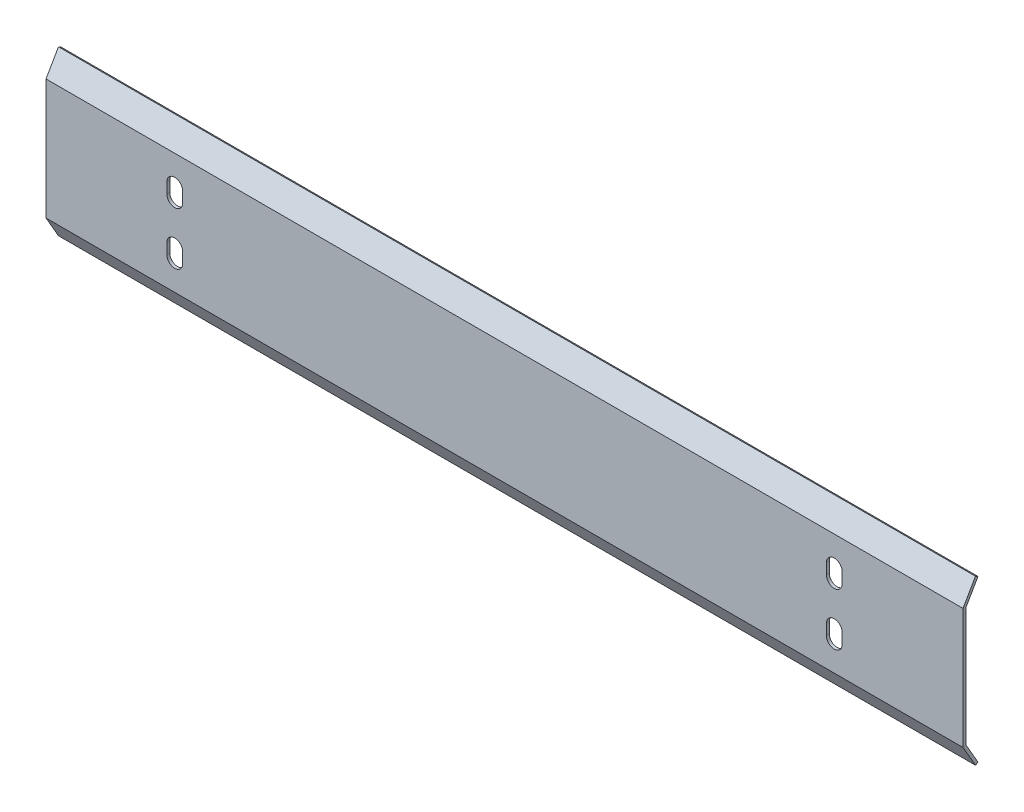
SolidWorks part; units mm, degrees
ref_plane "前视基准面" through (0, 0, 0) normal (0, 0, 1) x (1, 0, 0)
ref_plane "上视基准面" through (0, 0, 0) normal (0, 1, 0) x (1, 0, 0)
ref_plane "右视基准面" through (0, 0, 0) normal (1, 0, 0) x (0, 0, -1)
sketch "草图2" plane through (0, 0, 0) normal (1, 0, 0) x (0, 0, -1)
  line L3 (0, 0) -> (0, 45.8455)
  line L4 (0, 45.8455) -> (4.75, 54.0728)
  line L5 (0, 0) -> (4.75, -8.2272)
  line L6 (1.1, 0.2947) -> (5.7026, -7.6772)
  line L7 (1.1, 0.2947) -> (1.1, 45.5508)
  line L8 (1.1, 45.5508) -> (5.7026, 53.5228)
  line L9 (4.75, -8.2272) -> (5.7026, -7.6772)
  line L10 (5.7026, 53.5228) -> (4.75, 54.0728)
  dimension "D1" = 150
  dimension "D2" = 150
  dimension "D3" = 9.5
  dimension "D4" = 62.3
  dimension "D5" = 1.1
base flange "基体-法兰2" sketch "草图2" thickness 349 reverse thickness direction no parameters "D1"=1
sketch "草图11" plane through (0, 0, 0) normal (0, 0, 1) x (1, 0, 0)
  line L0 (-49, 14.9228) -> (-49, 10.9228) construction
  line L1 (-46, 14.9228) -> (-46, 10.9228)
  line L2 (-52, 14.9228) -> (-52, 10.9228)
  line L3 (0, 45.8455) -> (0, 0) construction
  line L4 (0, 22.9228) -> (-67.8978, 22.9228) construction
  arc A0 (-46, 14.9228) -> (-52, 14.9228) centre (-49, 14.9228) ccw
  arc A1 (-52, 10.9228) -> (-46, 10.9228) centre (-49, 10.9228) ccw
  point P2 (-49, 12.9228)
  dimension "D2" = 3
  dimension "D1" = 49
  dimension "D3" = 4
  dimension "D4" = 10
extrude "切除-拉伸1" cut sketch "草图11" against normal blind 10 normal cut yes
ref_plane "基准面1" through (0, 22.9228, 0) normal (0, 1, 0) x (1, 0, 0)
mirror "镜向1" about plane through (0, 22.9228, 0) normal (0, 1, 0) of "切除-拉伸1"
pattern_linear "阵列(线性)1" count 2 spacing 251 along (-1, 0, 0) of "镜向1", "切除-拉伸1"
sketch "折弯-线3" [suppressed] plane through (0, 0, 0) normal (0, 1, 0) x (1, 0, 0)
sketch "边界框3" [suppressed] plane through (0, 0, 0) normal (0, 1, 0) x (1, 0, 0)
sheet metal parameters "钣金13" thickness 349 parameters "D1"=1
flat pattern "平板型式13" [suppressed]
sketch "折弯-线4" plane through (0, 0, 0) normal (0, 1, 0) x (1, 0, 0)
sketch "边界框4" [suppressed] plane through (0, 0, 0) normal (0, 1, 0) x (1, 0, 0)
sheet metal parameters "钣金14" thickness 349 parameters "D1"=1
flat pattern "平板型式13"
sketch "折弯-线4" plane through (0, 0, 0) normal (0, 1, 0) x (1, 0, 0)
sketch "边界框4" [suppressed] plane through (0, 0, 0) normal (0, 1, 0) x (1, 0, 0)
sheet metal parameters "钣金15" thickness 349 parameters "D1"=1
flat pattern "平板型式13"
sketch "折弯-线4" plane through (0, 0, 0) normal (0, 1, 0) x (1, 0, 0)
sketch "边界框4" [suppressed] plane through (0, 0, 0) normal (0, 1, 0) x (1, 0, 0)
sheet metal parameters "钣金16" thickness 349 parameters "D1"=1
flat pattern "平板型式13"
sketch "折弯-线4" plane through (0, 0, 0) normal (0, 1, 0) x (1, 0, 0)
sketch3d "边界框4" [suppressed]
  line L0 (5.7026, 54.0728, 0) -> (5.7026, -8.2272, 0) construction
  line L1 (0, 54.0728, 0) -> (0, -8.2272, 0) construction
  line L2 (5.7026, 54.0728, 0) -> (0, 54.0728, 0) construction
  line L3 (5.7026, -8.2272, 0) -> (0, -8.2272, 0) construction
equation "\"厚度@钣金\"= \"长度\""
equation "\"D4@草图2\"= \"宽度\""
equation "\"D5@草图2\"= \"厚度\""
equation "\"D1@阵列(线性)1\"= \"孔数\""
equation "\"D3@阵列(线性)1\"= \"孔距\""
